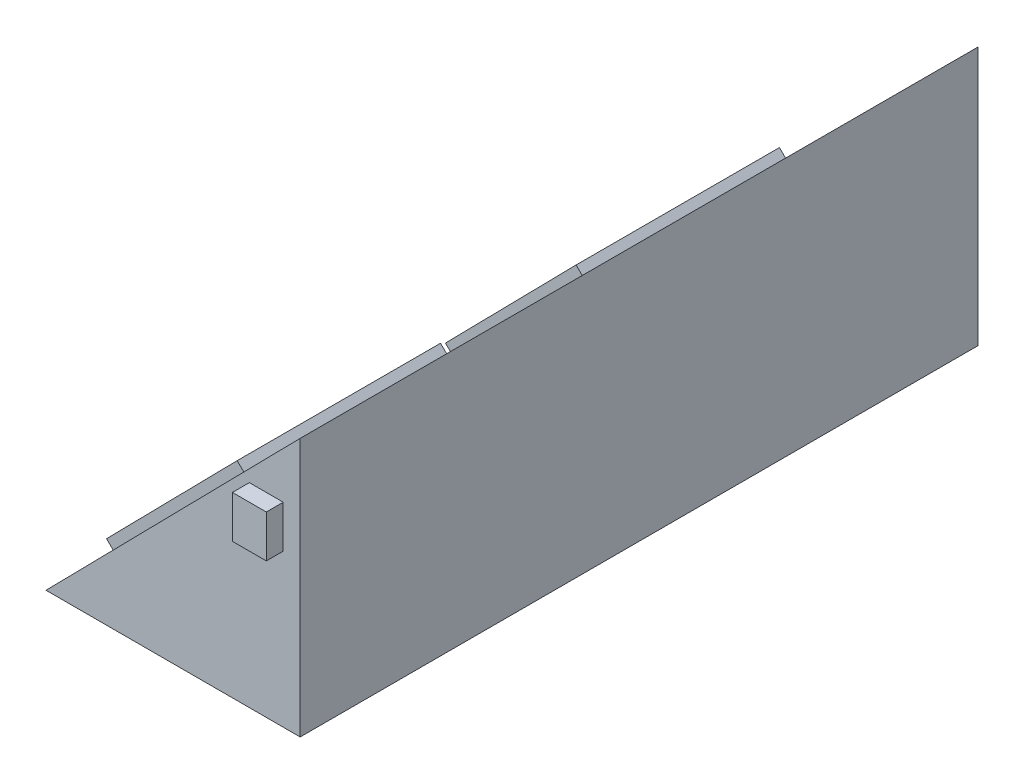
SolidWorks part; units mm, degrees
ref_plane "Front Plane" through (0, 0, 0) normal (0, 0, 1) x (1, 0, 0)
ref_plane "Top Plane" through (0, 0, 0) normal (0, 1, 0) x (1, 0, 0)
ref_plane "Right Plane" through (0, 0, 0) normal (1, 0, 0) x (0, 0, -1)
sketch "Sketch1" plane through (0, 0, 0) normal (0, 0, 1) x (1, 0, 0)
  line L0 (0, 0) -> (38.1, 38.7708)
  line L1 (38.1, 38.7708) -> (38.1, 0)
  line L2 (38.1, 0) -> (0, 0)
  dimension "D1" = 38.1
  dimension "D2" = 45.5
extrude "Boss-Extrude1" add sketch "Sketch1" along normal blind 101.6
sketch "Sketch2" plane through (0, 0, 101.6) normal (0, 0, 1) x (1, 0, 0)
  line L0 (0, 0) -> (38.1, 0) construction
  line L1 (30.48, 22.86) -> (35.56, 22.86)
  line L2 (30.48, 22.86) -> (30.48, 29.21)
  line L3 (30.48, 29.21) -> (35.56, 29.21)
  line L4 (35.56, 22.86) -> (35.56, 29.21)
  line L5 (38.1, 0) -> (38.1, 38.7708) construction
  dimension "D1" = 22.86
  dimension "D2" = 2.54
  dimension "D3" = 6.35
  dimension "D4" = 5.08
extrude "Boss-Extrude2" add sketch "Sketch2" along normal blind 2.54
extrude "Boss-Extrude3" add sketch "Sketch2<2>" against normal blind 2.54 from surface starting at face at (25.4, 12.9236, 0)
sketch "Sketch2<2>" plane through (0, 0, 101.6) normal (0, 0, 1) x (1, 0, 0) same geometry as "Sketch2"
sketch "Sketch3" plane through (0, 0, 0) normal (-0.7133, 0.7009, 0) x (0, 0, 1)
  line L0 (101.6, 0) -> (0, 0) construction
  line L1 (12.7, 0) -> (38.1, 0) construction
  line L2 (12.7, 0) -> (12.7, 25.4)
  line L3 (12.7, 25.4) -> (38.1, 25.4)
  line L4 (38.1, 0) -> (38.1, 25.4)
  line L5 (88.9, 0) -> (63.5, 0) construction
  line L6 (88.9, 0) -> (88.9, 25.4)
  line L7 (88.9, 25.4) -> (63.5, 25.4)
  line L8 (63.5, 0) -> (63.5, 25.4)
  line L9 (50.8, 54.358) -> (50.8, 0) construction
  line L10 (101.6, 54.358) -> (0, 54.358) construction
  line L11 (10.16, 0) -> (10.16, 27.94)
  line L12 (10.16, 27.94) -> (40.64, 27.94)
  line L13 (40.64, 0) -> (40.64, 27.94)
  line L14 (60.96, 0) -> (60.96, 27.94)
  line L15 (91.44, 27.94) -> (60.96, 27.94)
  line L16 (91.44, 0) -> (91.44, 27.94)
  line L17 (10.16, 0) -> (12.7, 0)
  line L18 (38.1, 0) -> (40.64, 0)
  line L19 (60.96, 0) -> (63.5, 0)
  line L20 (88.9, 0) -> (91.44, 0)
  dimension "D1" = 25.4
  dimension "D2" = 12.7
  dimension "D3" = 2.54
extrude "Boss-Extrude4" add sketch "Sketch3" along normal blind 1.524
